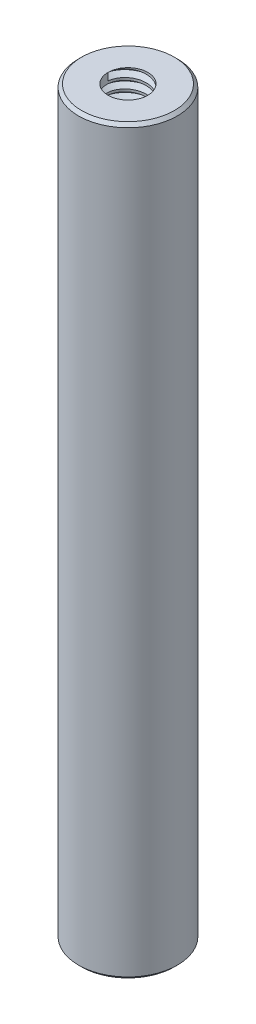
SolidWorks part; units mm, degrees
material "6061-T6 (SS)"
ref_plane "Alzado" through (0, 0, 0) normal (0, 0, 1) x (1, 0, 0)
ref_plane "Planta" through (0, 0, 0) normal (0, 1, 0) x (1, 0, 0)
ref_plane "Vista lateral" through (0, 0, 0) normal (1, 0, 0) x (0, 0, -1)
sketch "Croquis2" plane through (0, 0, 0) normal (0, 1, 0) x (1, 0, 0)
  circle A0 centre (0, 0) radius 6.35
  dimension "D1" = 12.7
extrude "Saliente-Extruir1" add sketch "Croquis2" along normal mid plane 95.25
chamfer "Chaflán1" distance 0.3969 angle 45 2 edges at (0, -47.625, 6.35) (0, 47.625, 6.35)
sketch "Croquis3" plane through (0, 0, 0) normal (0, 1, 0) x (1, 0, 0)
  circle A0 centre (0, 0) radius 2.5527
  dimension "D1" = 5.1054
extrude "Tap Hole 1" cut sketch "Croquis3" against normal blind 19.05 from surface starting at face at (0, 47.625, 5.9531)
extrude "Tap Hole 2" cut sketch "Croquis3<2>" along normal blind 19.05 from surface starting at face at (0, -47.625, 5.9531)
sketch "Croquis3<2>" plane through (0, 0, 0) normal (0, 1, 0) x (1, 0, 0) same geometry as "Croquis3"
sketch "Croquis4" plane through (0, 0, 0) normal (0, 1, 0) x (1, 0, 0)
  circle A0 centre (0, 0) radius 3.2639
  dimension "D1" = 6.5278
extrude "Clearance Hole" [suppressed] cut sketch "Croquis4" against normal through all both and the other way through all
thread "Rosca1" pitch 1.27 method cut profile "Perfil de rosca1" start angle 0, offset 0, length 0, pitch 1.27, diameter 5.1054
ref_plane "Plano1" through (-2.5527, 47.625, 0) normal (0, 0, 1) x (-1, 0, 0)
sketch "Perfil de rosca1" plane through (-2.5527, 47.625, 0) normal (0, 0, 1) x (-1, 0, 0)
  line L0 (0, 0) -> (0, 1.27) construction
  line L1 (0, 0) -> (0.6874, 0.3969)
  line L2 (0.6874, 0.3969) -> (0.6874, 0.5556)
  line L3 (0.6874, 0.5556) -> (0, 0.9525)
  line L4 (0.6874, 0.4762) -> (0, 0.4762) construction
  line L11 (0, 0) -> (0, 0.9525)
  point P2 (0, 0)
  dimension "Pitch" = 1.27
  dimension "Profile_Angle" = 60
  dimension "Profile_Land" = 0.1588
  dimension "Profile_Height" = 0.6874
thread "Rosca2" pitch 1.27 method cut profile "Perfil de rosca2" start angle 0, offset 0, length 0, pitch 1.27, diameter 5.1054
ref_plane "Plano2" through (2.5527, -47.625, 0) normal (0, 0, 1) x (1, 0, 0)
sketch "Perfil de rosca2" plane through (2.5527, -47.625, 0) normal (0, 0, 1) x (1, 0, 0)
  line L0 (0, 0) -> (0, 1.27) construction
  line L1 (0, 0) -> (0.6874, 0.3969)
  line L2 (0.6874, 0.3969) -> (0.6874, 0.5556)
  line L3 (0.6874, 0.5556) -> (0, 0.9525)
  line L4 (0.6874, 0.4762) -> (0, 0.4762) construction
  line L11 (0, 0) -> (0, 0.9525)
  point P2 (0, 0)
  dimension "Pitch" = 1.27
  dimension "Profile_Angle" = 60
  dimension "Profile_Land" = 0.1588
  dimension "Profile_Height" = 0.6874
equation "\"OD\" = 0.5pulgadas"
equation "\"Largo\"= 3.75pulgadas"
equation "\"Tap Hole\"= IIF ( \"OD\" = 0.375pulgadas , 0.1590pulgadas , 0.201pulgadas )"
equation "\"Spacer Hole\"= IIF ( \"OD\" = 0.375pulgadas , 0.196pulgadas , 0.257pulgadas )"
equation "\"D1@Croquis2\"=\"OD\""
equation "\"D1@Saliente-Extruir1\"=\"Largo\""
equation "\"D1@Croquis3\"=\"Tap Hole\""
equation "\"D1@Croquis4\"=\"Spacer Hole\""
